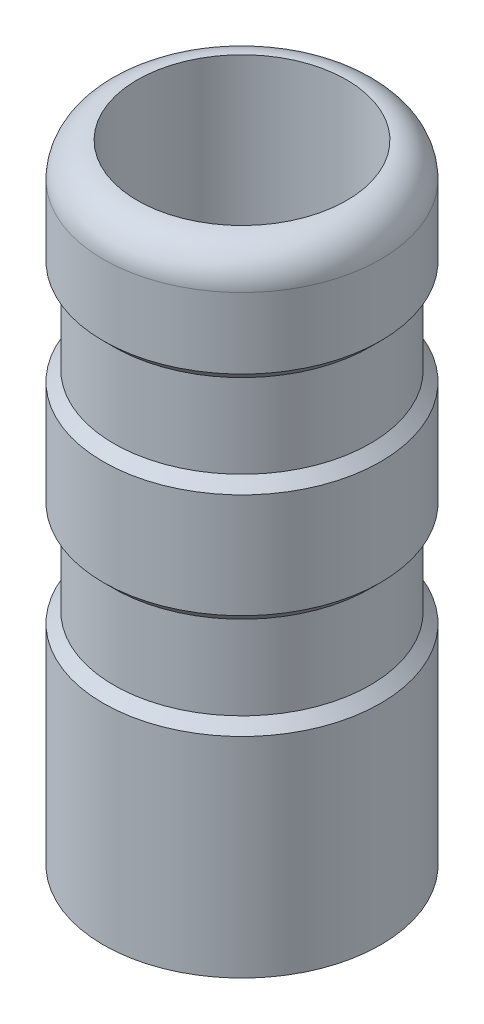
SolidWorks part; units mm, degrees
ref_plane "Front Plane" through (0, 0, 0) normal (0, 0, 1) x (1, 0, 0)
ref_plane "Top Plane" through (0, 0, 0) normal (0, 1, 0) x (1, 0, 0)
ref_plane "Right Plane" through (0, 0, 0) normal (1, 0, 0) x (0, 0, -1)
sketch "Sketch1" plane through (0, 0, 0) normal (0, 1, 0) x (1, 0, 0)
  circle A0 centre (0, 0) radius 12.7
  circle A1 centre (0, 0) radius 16.8275
  dimension "D1" = 33.655
  dimension "D2" = 25.4
extrude "Boss-Extrude1" add sketch "Sketch1" along normal blind 76.2
fillet "Fillet1" radius 4.1275 1 edges at (0, 76.2, 16.8275)
sketch "Sketch2" plane through (0, 0, 0) normal (0, 0, 1) x (1, 0, 0)
  line L0 (0, 0) -> (0, 76.2) construction
  line L1 (12.7, 76.2) -> (-12.7, 76.2) construction
  line L2 (16.8275, 63.5) -> (15.5575, 62.23)
  line L3 (16.8275, 0) -> (16.8275, 72.0725) construction
  line L4 (15.5575, 62.23) -> (15.5575, 52.07)
  line L5 (15.5575, 52.07) -> (16.8275, 50.8)
  line L6 (16.8275, 50.8) -> (16.8275, 63.5)
  line L7 (16.8275, 38.1) -> (15.5575, 36.83)
  line L8 (15.5575, 36.83) -> (15.5575, 26.67)
  line L9 (15.5575, 26.67) -> (16.8275, 25.4)
  line L10 (16.8275, 25.4) -> (16.8275, 38.1)
  point P9 (0, 0)
  dimension "D1" = 12.7
  dimension "D2" = 1.27
  dimension "D3" = 12.7
  dimension "D5" = 12.7
  dimension "D4" = 2
revolve "Cut-Revolve1" cut sketch "Sketch2" angle 360 about L0
